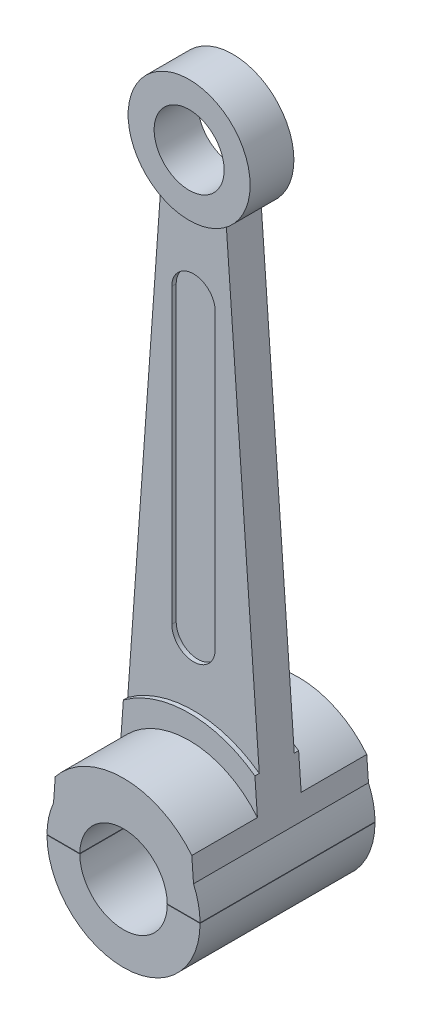
SolidWorks part; units mm, degrees
ref_plane "Front Plane" through (0, 0, 0) normal (0, 0, 1) x (1, 0, 0)
ref_plane "Top Plane" through (0, 0, 0) normal (0, 1, 0) x (1, 0, 0)
ref_plane "Right Plane" through (0, 0, 0) normal (1, 0, 0) x (0, 0, -1)
sketch "Sketch1" plane through (0, 0, 0) normal (0, 0, 1) x (1, 0, 0)
  line L0 (0, 0) -> (0, 13.69) construction
  line L1 (-0.75, 12.5138) -> (-1.65, 1.9311)
  line L2 (0.75, 12.5138) -> (1.65, 1.9311)
  line L3 (0, 10.69) -> (0, 4) construction
  line L8 (0.4963, 10.69) -> (0.4963, 4)
  line L9 (-0.4963, 10.69) -> (-0.4963, 4)
  circle A0 centre (0, 0) radius 2.54
  circle A1 centre (0, 0) radius 1
  circle A2 centre (0, 13.69) radius 0.8
  circle A3 centre (0, 13.69) radius 1.395
  arc A8 (0.4963, 10.69) -> (-0.4963, 10.69) centre (0, 10.69) ccw
  arc A9 (-0.4963, 4) -> (0.4963, 4) centre (0, 4) ccw
  point P13 (0, 7.345)
  dimension "D1" = 2
  dimension "D2" = 5.08
  dimension "D3" = 1.6
  dimension "D4" = 2.79
  dimension "D7" = 4
  dimension "D9" = 0.4963
  dimension "D5" = 13.69
  dimension "D6" = 1.5
  dimension "D8" = 3
  dimension "D10" = 3.3
extrude "Boss-Extrude1" add sketch "Sketch1" along normal mid plane 1 contours A3 A2 | A0 A1 region at (-0.6518, 14.8786, 0) region at (0, 2.4682, 0)
extrude "Boss-Extrude2" add sketch "Sketch1<3>" along normal mid plane 0.8 contours A3 L1 A0 L2 A9 L9 A8 L8 region at (0, 12.1841, 0)
sketch "Sketch1<3>" plane through (0, 0, 0) normal (0, 0, 1) x (1, 0, 0) same geometry as "Sketch1"
extrude "Boss-Extrude3" add sketch "Sketch1<4>" along normal mid plane 0.6 contours L9 A9 L8 A8 region at (0, 7.345, 0)
sketch "Sketch1<4>" plane through (0, 0, 0) normal (0, 0, 1) x (1, 0, 0) same geometry as "Sketch1"
sketch "Sketch2" plane through (0, 0, 0.5) normal (0, 0, 1) x (1, 0, 0)
  circle A0 centre (0, 0) radius 1
  circle A1 centre (0, 0) radius 2
  dimension "D1" = 4
  dimension "D2" = 2
extrude "Boss-Extrude4" add sketch "Sketch2" along normal blind 1.5 and the other way blind 2.5
sketch "Sketch3" plane through (0, 0, 0) normal (0, 0, 1) x (1, 0, 0)
  line L0 (-2.4415, 2.5078) -> (-0.75, 12.5138)
  line L1 (-0.75, 12.5138) -> (-1.6, 0.7089)
  line L2 (2.4415, 2.5078) -> (0.75, 12.5138)
  line L3 (0.75, 12.5138) -> (1.6, 0.7089)
  arc A0 (-1.6, 0.7089) -> (1.6, 0.7089) centre (0, 0) ccw
  arc A1 (-2.4415, 2.5078) -> (2.4415, 2.5078) centre (0, 0) ccw
  dimension "D2" = 1.75
  dimension "D3" = 3.5
  dimension "D1" = 3.2
extrude "Cut-Extrude1" cut sketch "Sketch3" against normal mid plane 31.5
sketch "Sketch4" plane through (0, 0, 0) normal (0, 0, 1) x (1, 0, 0)
  line L0 (0, 0) -> (7.1069, 0) construction
  line L2 (7.1069, 0) -> (-4.826, 0)
  line L3 (7.1069, 0) -> (7.1069, 0.01)
  line L4 (7.1069, 0.01) -> (-4.826, 0.01)
  line L5 (-4.826, 0) -> (-4.826, 0.01)
  dimension "D1" = 0.01
extrude "Cut-Extrude2" cut sketch "Sketch4" against normal mid plane 31.5
